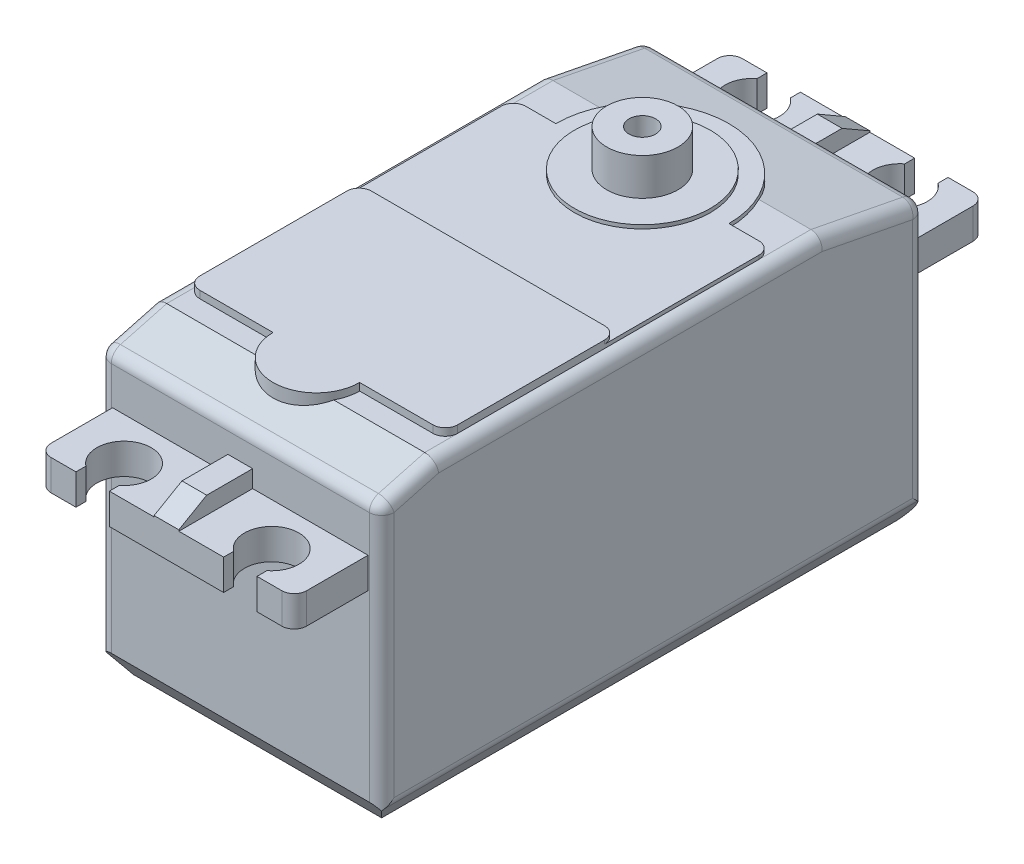
SolidWorks part; units mm, degrees
note: The reader was unsure of these and kept them because the rebuilt part matched: shared geometry of "Эскиз7<2>".
material "ПК/АБС"
ref_plane "Спереди" through (0, 0, 0) normal (0, 0, 1) x (1, 0, 0)
ref_plane "Сверху" through (0, 0, 0) normal (0, 1, 0) x (1, 0, 0)
ref_plane "Справа" through (0, 0, 0) normal (1, 0, 0) x (0, 0, -1)
ref_plane "Плоскость1" through (11.43, 0, 0) normal (1, 0, 0) x (0, 0, -1)
sketch "Эскиз1" plane through (11.43, 0, 0) normal (1, 0, 0) x (0, 0, -1)
  line L0 (-38.481, -24.55) -> (17.399, -24.55)
  line L1 (17.399, -24.55) -> (17.399, 0)
  line L2 (17.399, 0) -> (-38.481, 0)
  line L3 (-38.481, 0) -> (-38.481, -24.55)
  dimension "D1" = 55.88
  dimension "D2" = 24.55
  dimension "D3" = 17.399
extrude "Бобышка-Вытянуть1" add sketch "Эскиз1" against normal blind 22.86
sketch "Эскиз2" plane through (-11.43, 0, 0) normal (-1, 0, 0) x (0, 0, 1)
  line L0 (-17.399, -24.55) -> (-11.43, -24.55)
  line L1 (-11.43, -24.55) -> (-11.43, -7.786)
  line L2 (-11.43, -7.786) -> (-17.399, -7.786)
  line L3 (-17.399, -7.786) -> (-17.399, -24.55)
  line L5 (-17.399, -24.55) -> (-17.399, 0) construction
  line L6 (38.481, -24.55) -> (-17.399, -24.55) construction
  line L9 (38.481, -24.55) -> (32.512, -24.55)
  line L10 (38.481, -24.55) -> (38.481, -7.786)
  line L11 (38.481, -7.786) -> (32.512, -7.786)
  line L12 (32.512, -24.55) -> (32.512, -7.786)
  dimension "D1" = 16.764
  dimension "D2" = 5.969
extrude "Вырез-Вытянуть1" cut sketch "Эскиз2" against normal through all
sketch "Эскиз3" plane through (-11.43, 0, 0) normal (-1, 0, 0) x (0, 0, 1)
  line L0 (-17.399, 0) -> (-17.399, -5.306)
  line L1 (-17.399, -5.306) -> (-11.43, -5.306)
  line L2 (-11.43, -5.306) -> (-11.43, 0)
  line L3 (-11.43, 0) -> (-17.399, 0)
  line L6 (-11.43, -7.786) -> (-17.399, -7.786) construction
  line L7 (38.481, 0) -> (32.512, 0)
  line L8 (32.512, 0) -> (32.512, -5.306)
  line L9 (32.512, -5.306) -> (38.481, -5.306)
  line L10 (38.481, -5.306) -> (38.481, 0)
  dimension "D1" = 5.969
  dimension "D2" = 2.48
extrude "Вырез-Вытянуть2" cut sketch "Эскиз3" against normal through all
sketch "Эскиз7" plane through (0, 0, -11.43) normal (0, 0, -1) x (-1, 0, 0)
  line L0 (-1, -5.306) -> (-1, -3.906)
  line L1 (-1, -3.906) -> (1, -3.906)
  line L2 (1, -3.906) -> (1, -5.306)
  line L3 (1, -5.306) -> (-1, -5.306)
  line L5 (-11.43, -5.306) -> (11.43, -5.306) construction
  point P4 (0, -5.306)
  dimension "D1" = 2
  dimension "D2" = 1.4
extrude "Бобышка-Вытянуть2" add sketch "Эскиз7" along normal up to surface (5.969 mm away) up to face at (0, -6.546, -17.399)
extrude "Бобышка-Вытянуть5" add sketch "Эскиз7<2>" against normal up to surface (5.969 mm away) from surface at -43.942 up to face at (0, -6.546, 38.481) starting at face at (0, -2.653, 32.512)
sketch "Эскиз7<2>" plane through (0, 0, -11.43) normal (0, 0, -1) x (-1, 0, 0) same geometry as "Эскиз7"
sketch "Эскиз5" plane through (0, -5.306, 0) normal (0, 1, 0) x (-1, 0, 0)
  line L0 (4.62, -17.399) -> (7.32, -17.399)
  line L1 (7.32, -17.399) -> (7.32, -16.5961)
  line L2 (4.62, -16.5961) -> (4.62, -17.399)
  line L3 (-11.43, -17.399) -> (-1, -17.399) construction
  line L4 (1, -17.399) -> (11.43, -17.399) construction
  line L5 (-7.32, -17.399) -> (-4.62, -17.399)
  line L6 (-4.62, -17.399) -> (-4.62, -16.5961)
  line L7 (-7.32, -16.5961) -> (-7.32, -17.399)
  line L8 (-11.43, -17.399) -> (-1, -17.399) construction
  line L9 (-11.43, 10.541) -> (11.43, 10.541) construction
  line L10 (-11.43, -11.43) -> (-11.43, 32.512) construction
  line L11 (11.43, -11.43) -> (11.43, 32.512) construction
  line L12 (-7.32, 37.6781) -> (-7.32, 38.481)
  line L13 (-4.62, 38.481) -> (-4.62, 37.6781)
  line L14 (-7.32, 38.481) -> (-4.62, 38.481)
  line L15 (4.62, 37.6781) -> (4.62, 38.481)
  line L16 (7.32, 38.481) -> (7.32, 37.6781)
  line L17 (4.62, 38.481) -> (7.32, 38.481)
  arc A0 (7.32, -16.5961) -> (4.62, -16.5961) centre (5.97, -14.859) ccw
  arc A1 (-4.62, -16.5961) -> (-7.32, -16.5961) centre (-5.97, -14.859) ccw
  arc A2 (-4.62, 37.6781) -> (-7.32, 37.6781) centre (-5.97, 35.941) cw
  arc A3 (7.32, 37.6781) -> (4.62, 37.6781) centre (5.97, 35.941) cw
  dimension "D1" = 2.54
  dimension "D2" = 2.2
  dimension "D3" = 11.94
  dimension "D4" = 5.97
  dimension "D5" = 2.7
extrude "Вырез-Вытянуть4" cut sketch "Эскиз5" against normal through all
sketch "Эскиз12" plane through (0, 0, -11.43) normal (0, 0, -1) x (-1, 0, 0)
  line L0 (3.5, -18.05) -> (3.5, -22.05)
  line L1 (3.5, -22.05) -> (-3.5, -22.05)
  line L2 (-3.5, -22.05) -> (-3.5, -18.05)
  line L3 (-3.5, -18.05) -> (3.5, -18.05)
  line L4 (-11.43, -24.55) -> (11.43, -24.55) construction
  point P6 (0, -18.05)
  dimension "D1" = 7
  dimension "D2" = 4
  dimension "D3" = 2.5
extrude "Бобышка-Вытянуть4" add sketch "Эскиз12" along normal blind 6 draft 6
sketch "Эскиз13" plane through (0, 0, 0) normal (0, 0, 1) x (1, 0, 0)
  line L0 (2.88, 3.3) -> (1.075, 3.3)
  line L1 (1.075, 0) -> (5.49, 0)
  line L2 (1.075, 3.3) -> (1.075, 0)
  line L3 (5.49, 0) -> (5.49, 0.3)
  line L4 (5.49, 0.3) -> (2.88, 0.3)
  line L5 (2.88, 0.3) -> (2.88, 3.3)
  line L6 (0, 3.7769) -> (0, 0) construction
  dimension "D1" = 5.76
  dimension "D2" = 10.98
  dimension "D3" = 3.3
  dimension "D4" = 0.3
  dimension "D5" = 2.15
revolve "Повернуть1" add sketch "Эскиз13" angle 360 about L6
chamfer "Фаска1" distance 1.3 angle 60 2 edges at (0, -3.906, -17.399) (0, -3.906, 38.481)
sketch "Эскиз18" plane through (0, 0, 0) normal (0, 1, 0) x (1, 0, 0)
  line L0 (7, 0) -> (9.425, 0)
  line L1 (10.425, -1) -> (10.425, -25.36)
  line L2 (9.425, -26.36) -> (3.5, -26.36)
  line L3 (-3.5, -26.36) -> (-9.425, -26.36)
  line L4 (-10.425, -25.36) -> (-10.425, -1)
  line L5 (-9.425, 0) -> (-7, 0)
  arc A0 (-3.5, -26.36) -> (3.5, -26.36) centre (0, -26.36) ccw
  arc A1 (-7, 0) -> (7, 0) centre (0, 0) cw
  arc A2 (9.425, 0) -> (10.425, -1) centre (9.425, -1) cw
  arc A3 (10.425, -25.36) -> (9.425, -26.36) centre (9.425, -25.36) cw
  arc A4 (-9.425, -26.36) -> (-10.425, -25.36) centre (-9.425, -25.36) cw
  arc A5 (-10.425, -1) -> (-9.425, 0) centre (-9.425, -1) cw
  line M2 (-11.43, -32.512) -> (11.43, -32.512)
  line M3 (11.43, -32.512) -> (11.43, 11.43)
  line M4 (11.43, 11.43) -> (-11.43, 11.43)
  line M5 (-11.43, 11.43) -> (-11.43, -32.512)
  dimension "D1" = 7
  dimension "D2" = 3.5
  dimension "D5" = 1
  dimension "D3" = 20.85
  dimension "D4" = 26.36
extrude "Вырез-Вытянуть9" cut sketch "Эскиз18" against normal blind 0.3 contours L4 A5 L5 A1 L0 A2 L1 A3 L2 A0 L3 A4 M5 M2 M3 M4
sketch "Эскиз19" plane through (0, 0, 0) normal (0, 1, 0) x (1, 0, 0)
  line L0 (10.425, -1) -> (10.425, -25.36) construction
  line L2 (-10.425, -25.36) -> (-10.425, -1) construction
  line L3 (-9.425, -12.48) -> (9.425, -12.48)
  line L4 (10.425, -1) -> (10.425, -25.36) construction
  line L5 (9.425, -26.36) -> (3.5, -26.36) construction
  line L6 (-10.425, -13.48) -> (-10.425, -25.36)
  line L7 (-9.425, -26.36) -> (-3.5, -26.36)
  line L8 (3.5, -26.36) -> (9.425, -26.36)
  line L9 (10.425, -25.36) -> (10.425, -13.48)
  arc A0 (10.425, -13.48) -> (9.425, -12.48) centre (9.425, -13.48) ccw
  arc A1 (-10.425, -13.48) -> (-9.425, -12.48) centre (-9.425, -13.48) cw
  arc A2 (10.425, -25.36) -> (9.425, -26.36) centre (9.425, -25.36) cw
  arc A3 (-9.425, -26.36) -> (-10.425, -25.36) centre (-9.425, -25.36) cw
  arc A4 (3.5, -26.36) -> (-3.5, -26.36) centre (0, -26.36) cw
  dimension "D1" = 1
  dimension "D2" = 13.88
extrude "Бобышка-Вытянуть6" add sketch "Эскиз19" along normal blind 0.3
sketch "Эскиз20" plane through (11.43, 0, 0) normal (1, 0, 0) x (0, 0, -1)
  line L0 (11.43, -5.306) -> (11.43, -7.786)
  line L1 (-32.512, -7.786) -> (-32.512, -5.306)
  line M4 (-32.512, -5.306) -> (-38.481, -5.306)
  line M5 (-38.481, -5.306) -> (-38.481, -7.786)
  line M6 (-38.481, -7.786) -> (-32.512, -7.786)
  line M10 (11.43, -7.786) -> (17.399, -7.786)
  line M11 (17.399, -7.786) -> (17.399, -5.306)
  line M12 (17.399, -5.306) -> (11.43, -5.306)
extrude "Вырез-Вытянуть10" cut sketch "Эскиз20" against normal blind 1.1 contours L1 M6 M4 M5 | L0 M12 M10 M11
sketch "Эскиз21" plane through (-11.43, 0, 0) normal (-1, 0, 0) x (0, 0, 1)
  line L0 (-11.43, -5.306) -> (-11.43, -7.786)
  line L1 (32.512, -7.786) -> (32.512, -5.306)
  line M3 (-11.43, -5.306) -> (-17.399, -5.306)
  line M4 (-17.399, -5.306) -> (-17.399, -7.786)
  line M5 (-17.399, -7.786) -> (-11.43, -7.786)
  line M9 (32.512, -7.786) -> (38.481, -7.786)
  line M10 (38.481, -7.786) -> (38.481, -5.306)
  line M11 (38.481, -5.306) -> (32.512, -5.306)
extrude "Вырез-Вытянуть11" cut sketch "Эскиз21" against normal blind 1.1 contours L0 M3 M4 M5 | L1 M9 M10 M11
chamfer "Фаска3" distance 1.6 angle 79 1 edges at (0, -0.3, -11.43)
chamfer "Фаска4" distance 1.2 angle 75 1 edges at (0, -0.3, 32.512)
chamfer "Фаска5" distance 2 angle 35 3 edges at (11.43, -24.55, 10.541) (-11.43, -24.55, 10.541) (0, -24.55, 32.512)
fillet "Скругление1" radius 1 19 edges at (11.43, -12.225, -11.43) (-11.43, -12.225, -11.43) (-11.43, -12.025, 32.512) (11.43, -12.025, 32.512) (10.33, -6.546, 38.481) (-10.33, -6.546, 38.481) (10.33, -6.546, -17.399) (-10.33, -6.546, -17.399) (-11.43, -0.9, 30.2728) (-11.43, -0.3, 12.4174) (-11.43, -1.1, -7.3144) (0, -1.9, -11.43) (11.43, -1.1, -7.3144) (11.43, -0.3, 12.4174) (11.43, -0.9, 30.2728) (0, -1.5, 32.512) (11.43, -22.55, 10.541) (-11.43, -22.55, 10.541) (0, -24.55, -11.43)
sketch "Эскиз23" plane through (-1, 0, 0) normal (-1, 0, 0) x (0, 0, 1)
  line L0 (-14.23, -3.906) -> (-14.23, -5.306)
  line L1 (-15.1473, -3.906) -> (-11.43, -3.906) construction
  line L2 (-17.399, -5.306) -> (-11.43, -5.306) construction
  line L3 (-14.23, -5.306) -> (-17.399, -5.306)
  line L4 (-11.43, -5.306) -> (-11.43, -3.906) construction
  dimension "D1" = 2.8
extrude "доработка" [suppressed] cut sketch "Эскиз23" against normal through all flip side to cut
